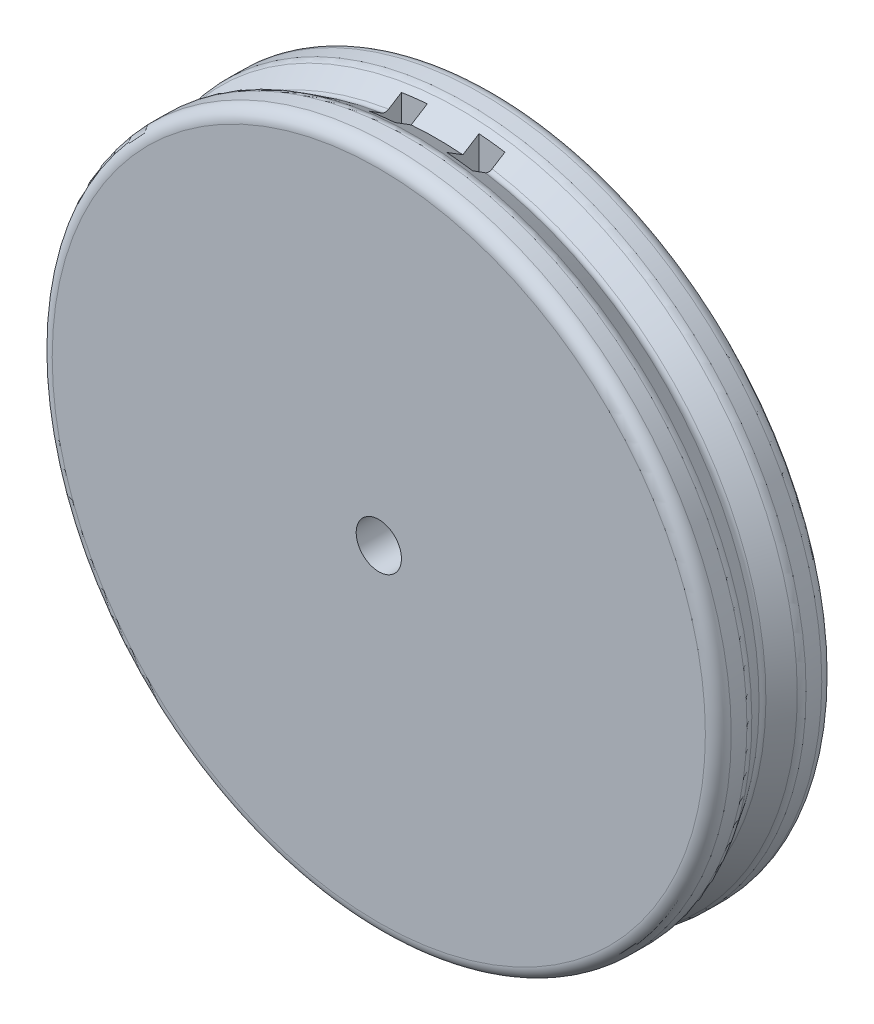
SolidWorks part; units mm, degrees
ref_plane "Front Plane" through (0, 0, 0) normal (0, 0, 1) x (1, 0, 0)
ref_plane "Top Plane" through (0, 0, 0) normal (0, 1, 0) x (1, 0, 0)
ref_plane "Right Plane" through (0, 0, 0) normal (1, 0, 0) x (0, 0, -1)
sketch "Sketch1" plane through (0, 0, 0) normal (0, 0, 1) x (1, 0, 0)
  circle A0 centre (0, 0) radius 50
  dimension "D1" = 100
extrude "Boss-Extrude1" add sketch "Sketch1" along normal mid plane 8
sketch "Sketch2" plane through (0, 0, 4) normal (0, 0, 1) x (1, 0, 0)
  circle A0 centre (0, 0) radius 52.5
  dimension "D1" = 105
extrude "Boss-Extrude2" add sketch "Sketch2" along normal blind 5
sketch "Sketch6" plane through (0, 0, 0) normal (1, 0, 0) x (0, 0, -1)
  line L0 (-4, 52.5) -> (0, 50)
  line L1 (4, 50) -> (-4, 50) construction
  line L2 (0, 50) -> (-4, 50)
  line L3 (-4, 50) -> (-4, 52.5)
  line L4 (-30.4204, 0) -> (21.2132, 0) construction
revolve "Revolve1" add sketch "Sketch6" angle 360 about L4
mirror "Mirror1" about plane through (0, 0, 0) normal (0, 0, 1) of "Revolve1", "Boss-Extrude2"
ref_plane "Plane3" through (0, 0, 0) normal (0, 0, 1) x (1, 0, 0)
sketch "Sketch7" plane through (0, 0, 0) normal (0, 0, 1) x (1, 0, 0)
  line L0 (0, 37.5) -> (0, -52.5) construction
  line L3 (-4, 37.5) -> (-4, 52.3474)
  line L4 (-8, 37.5) -> (-8, 51.8869)
  line L5 (0, 37.5) -> (15.7968, 37.5) construction
  line L6 (4, 37.5) -> (4, 52.3474)
  line L7 (8, 37.5) -> (8, 51.8869)
  arc A2 (-4, 37.5) -> (4, 37.5) centre (0, 37.5) ccw
  arc A3 (-8, 37.5) -> (8, 37.5) centre (0, 37.5) ccw
  circle A6 centre (0, 0) radius 52.5 construction
  arc A7 (8, 51.8869) -> (4, 52.3474) centre (0, 0) ccw
  arc A8 (-4, 52.3474) -> (-8, 51.8869) centre (0, 0) ccw
  circle A9 centre (0, 0) radius 52.5 construction
  circle A10 centre (0, 0) radius 52.5 construction
  dimension "D1" = 4
  dimension "D2" = 8
  dimension "D3" = 37.5
extrude "Cut-Extrude4" cut sketch "Sketch7" against normal mid plane 5
sketch "Sketch4" plane through (0, 0, -9) normal (0, 0, -1) x (-1, 0, 0)
  circle A0 centre (0, 0) radius 3.5
  dimension "D1" = 7
extrude "Cut-Extrude3" cut sketch "Sketch4" against normal through all
fillet "Fillet2" radius 1 1 edges at (0, -50, 0)
fillet "Fillet3" radius 2 4 edges at (52.5, 0, -4) (52.5, 0, 4) (52.5, 0, 9) (52.5, 0, -9)
